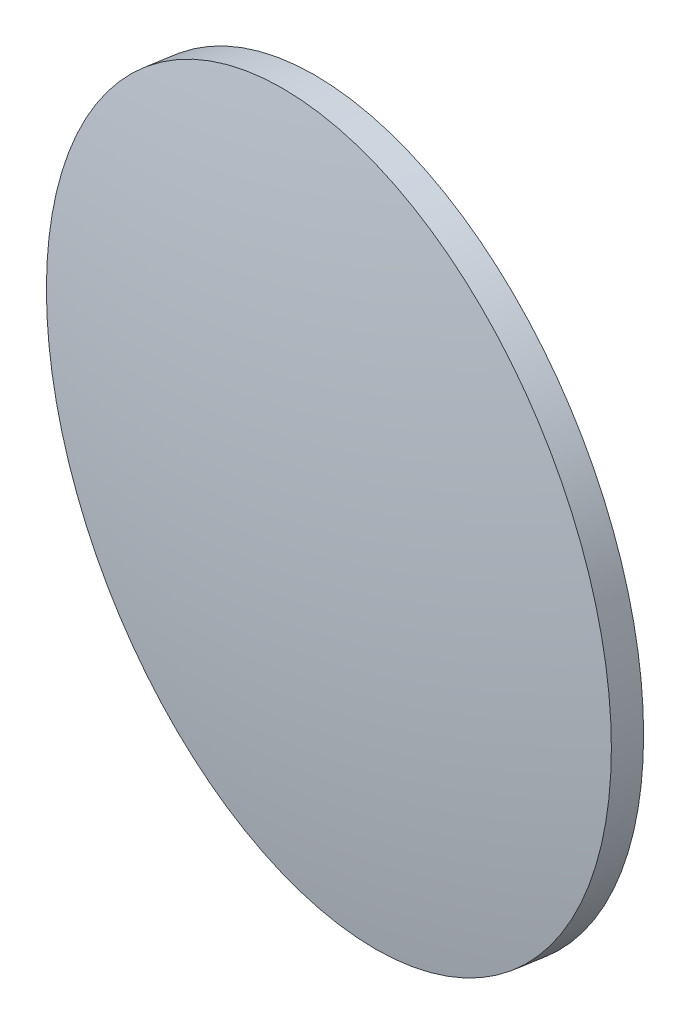
SolidWorks part; units mm, degrees
ref_plane "Front Plane" through (0, 0, 0) normal (0, 0, 1) x (1, 0, 0)
ref_plane "Top Plane" through (0, 0, 0) normal (0, 1, 0) x (1, 0, 0)
ref_plane "Right Plane" through (0, 0, 0) normal (1, 0, 0) x (0, 0, -1)
sketch "Sketch1" plane through (0, 0, 0) normal (1, 0, 0) x (0, 0, -1)
  line L0 (4.196, 50) -> (0.14, 50)
  line L1 (0.14, -50) -> (4.196, -50)
  line L2 (-4, 259.3798) -> (-4, -259.3798) construction
  arc A0 (4.196, -50) -> (4.196, 50) centre (300, 0) cw
  arc A1 (0.14, -50) -> (0.14, 50) centre (300, 0) cw
  arc A2 (0.252, -50.6667) -> (0.252, 50.6667) centre (300, 0) cw construction
  point P3 (0, 0)
  point P12 (-4, 0)
  point P13 (-4, 0)
  dimension "D1" = 300
  dimension "D2" = 100
  dimension "D3" = 4
sketch "Sketch2" plane through (0, 0, 0) normal (0, 1, 0) x (1, 0, 0)
  line L0 (0, 0) -> (0, 4.196) construction
  arc A0 (-98.6013, 16.6667) -> (0, 0) centre (0, 300) ccw
  point P3 (-50, 4.196)
  dimension "D1" = 300
  dimension "D2" = 100
sweep "Sweep2" add profiles "Sketch1" path "Sketch2"
ref_plane "Plane1" through (-50.6667, 0, -0.252) normal (-0.1667, 0, 0.986) x (0.986, 0, 0.1667)
sketch "Sketch4" plane through (-0.8119, 0, 8.175) normal (-0.1667, 0, 0.986) x (0.986, 0, 0.1667)
  line L4 (14.2987, 66.5625) -> (-121.8505, 66.5625)
  line L5 (14.2987, 66.5625) -> (14.2987, -69.9074)
  line L6 (14.2987, -69.9074) -> (-121.8505, -69.9074)
  line L7 (-121.8505, 66.5625) -> (-121.8505, -69.9074)
  circle A0 centre (-50.5619, 0) radius 50
  ellipse E0 centre (-50.5619, 0) end of major axis (-50.5619, 300) minor radius 50 (-99.8626, 50) -> (-99.8626, -50) ccw construction
  ellipse E1 centre (-50.5619, 0) end of major axis (-50.5619, 300) minor radius 50 (-99.8626, 50) -> (-99.8626, -50) ccw construction
  ellipse E2 centre (-50.5619, 0) end of major axis (-50.5619, -304) minor radius 50.6667 (-0.5853, -50) -> (-0.5853, 50) ccw construction
  ellipse E3 centre (-50.5619, 0) end of major axis (-50.5619, -304) minor radius 50.6667 (-0.5853, -50) -> (-0.5853, 50) ccw construction
  point P16 (-50.5619, 0)
  dimension "D1" = 100
extrude "Cut-Extrude2" cut sketch "Sketch4" against normal through all
